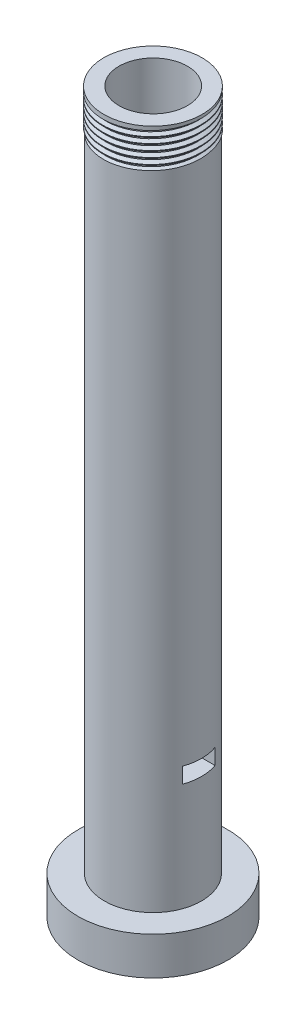
SolidWorks part; units mm, degrees
note: '?' marks a value the reader was unsure of.
material "ABS"
ref_plane "Front Plane" through (0, 0, 0) normal (0, 0, 1) x (1, 0, 0)
ref_plane "Top Plane" through (0, 0, 0) normal (0, 1, 0) x (1, 0, 0)
ref_plane "Right Plane" through (0, 0, 0) normal (1, 0, 0) x (0, 0, -1)
sketch "Sketch1" plane through (0, 0, 0) normal (1, 0, 0) x (0, 0, -1)
  line L0 (-11.5458, 84.0619) -> (-11.5458, 75.1997)
  line L1 (-11.5458, 75.1997) -> (11.28, 75.1997)
  line L3 (-11.4128, -75.1997) -> (11.28, -75.1997)
  line L4 (11.28, 75.1997) -> (11.28, -75.1997)
  line L5 (-11.4128, -75.1997) -> (-11.4128, 75.1997)
  line L7 (-8.0628, -50) -> (7.9372, -50)
  line L8 (-8.0628, -50) -> (-8.0628, 50)
  line L9 (-8.0628, 50) -> (7.9372, 50)
  line L10 (7.9372, -50) -> (7.9372, 50)
  line L11 (-8.0628, -50) -> (7.9372, 50) construction
  line L12 (-8.0628, 50) -> (7.9372, -50) construction
  line L13 (-11.5458, 84.0619) -> (11.4202, 84.0619)
  line L14 (-11.5458, 75.1997) -> (11.4202, 75.1997)
  line L15 (11.4202, 84.0619) -> (11.4202, 75.1997)
  line L16 (-0.0628, 75.1997) -> (-0.0628, 84.0619) construction
  line L17 (-21.3591, 84.0619) -> (21.3591, 84.0619) construction
  line L18 (-14.8981, 0) -> (11.28, 0) construction
  line L19 (-17.593, -75.1997) -> (17.4674, -75.1997)
  line L20 (17.4674, -84.0619) -> (17.4674, -75.1997)
  line L21 (-17.593, -84.0619) -> (17.4674, -84.0619)
  line L22 (-17.593, -84.0619) -> (-17.593, -75.1997)
  line L23 (-0.0628, 84.0619) -> (-0.0628, -84.0619)
  point P0 (0, 0)
  point P5 (-0.0628, 0)
  point P12 (-0.0628, 84.0619)
  point P18 (-0.0628, 50)
revolve "Revolve1" add sketch "Sketch1" angle 360 about L23
ref_plane "Plane1" through (0, 84.0619, 0) normal (0, 1, 0) x (1, 0, 0)
sketch "Sketch2" plane through (0, 84.0619, 0) normal (0, 1, 0) x (1, 0, 0)
  circle A1 centre (0, 0) radius 8
extrude "Cut-Extrude1" cut sketch "Sketch2" along direction (0, -1, 0) on the side against the normal up to vertex (134.0619 mm away) up to point (0, -50, -7.9372)
ref_plane "Plane2" through (0, 75.1997, 0) normal (0, -1, 0) x (-1, 0, 0)
sketch "Sketch3" plane through (0, 75.1997, 0) normal (0, -1, 0) x (-1, 0, 0)
  circle A0 centre (0, -0.0628) radius 21.2963
ref_plane "Plane3" through (0, -75.1997, 0) normal (0, 1, 0) x (1, 0, 0)
sketch "Sketch5" plane through (0, -75.1997, 0) normal (0, 1, 0) x (1, 0, 0)
  circle A0 centre (0, 0) radius 21.3591
thread "Thread5" pitch 1.4111 method cut profile "Thread Profile5" start angle 0, offset 0, length 0, pitch 1.4111, diameter 22.966
ref_plane "Plane8" through (-11.483, 84.0619, 0.0628) normal (0, 0, 1) x (-1, 0, 0)
sketch "Thread Profile5" plane through (-11.483, 84.0619, 0.0628) normal (0, 0, 1) x (-1, 0, 0)
  line L0 (0, 0) -> (0, 1.4111) construction
  line L11 (0, 0) -> (0, 1.2347)
  line L12 (0, 1.2347) -> (-0.7638, 0.7937)
  line L13 (-0.7638, 0.7937) -> (-0.7638, 0.441)
  line L15 (-0.7638, 0.441) -> (0, 0)
  line L17 (-0.7638, 0.6174) -> (0, 0.6174) construction
  point P2 (0, 0)
  dimension "Pitch" = 1.4111
  dimension "Profile_Angle" = 60
  dimension "Profile_Land" = 0.3528
  dimension "Profile_Height" = 0.7638
ref_axis "Axis1" through (0, -50, 0) along (0, 1, 0)?
ref_axis "Axis2" through (0, 84.0619, 11.5458) along (0, 0, -1)?
ref_plane "Plane9" through (0, 0, 0) normal (1, 0, 0) x (0, 0, -1)
sketch "Sketch20" plane through (0, 0, 0) normal (1, 0, 0) x (0, 0, -1)
  line L0 (-3.8764, -46.3484) -> (-3.8764, -50)
  line L1 (-3.8764, -46.3484) -> (3.7508, -46.3484)
  line L2 (-3.8764, -50) -> (3.7508, -50)
  line L3 (3.7508, -46.3484) -> (3.7508, -50)
  line L4 (-0.0628, -50) -> (-0.0628, -46.3484) construction
  line L5 (-3.8764, -48.1742) -> (3.7508, -48.1742) construction
  point P1 (-0.0628, -48.1742)
extrude "Cut-Extrude2" cut sketch "Sketch20" against normal up to surface and the other way up to surface up to face at (2.1359, 74.6233, -10.6715) other way up to face at (2.1359, 74.6233, -10.6715)
